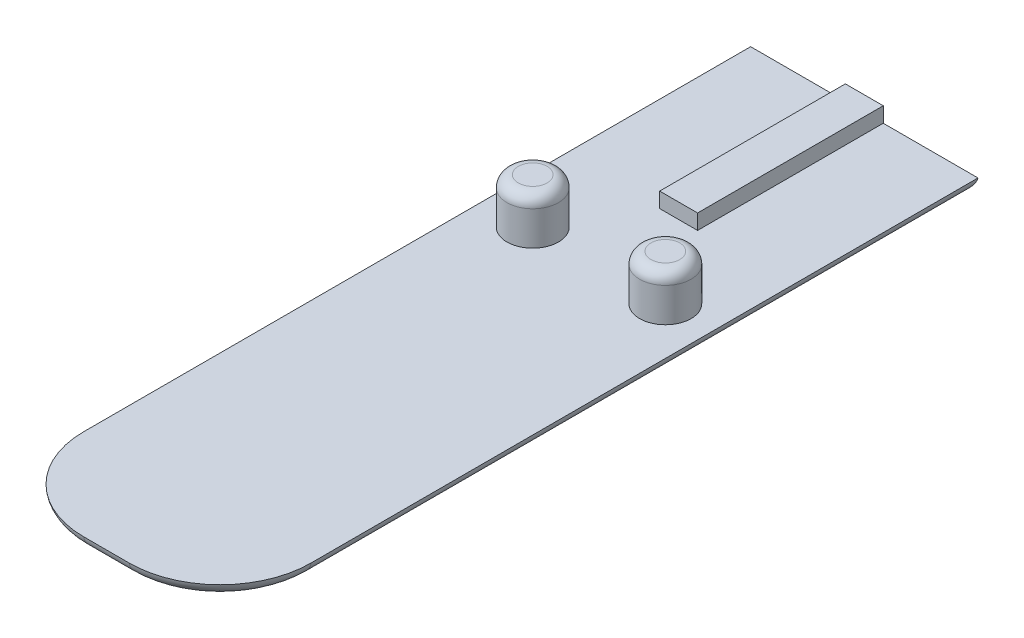
SolidWorks part; units mm, degrees
ref_plane "Front Plane" through (0, 0, 0) normal (0, 0, 1) x (1, 0, 0)
ref_plane "Top Plane" through (0, 0, 0) normal (0, 1, 0) x (1, 0, 0)
ref_plane "Right Plane" through (0, 0, 0) normal (1, 0, 0) x (0, 0, -1)
sketch "Sketch1" plane through (0, 0, 0) normal (0, 1, 0) x (1, 0, 0)
  line L0 (0, 50) -> (0, -50) construction
  line L1 (-15, -50) -> (15, -50)
  line L2 (-15, -50) -> (-15, 50)
  line L3 (-15, 50) -> (15, 50)
  line L4 (15, -50) -> (15, 50)
  line L5 (-15, -50) -> (15, 50) construction
  line L6 (-15, 50) -> (15, -50) construction
  point P0 (0, 0)
  dimension "D1" = 100
  dimension "D2" = 30
extrude "Boss-Extrude1" add sketch "Sketch1" along normal blind 1.7 contours L2 L1 L4 L3
fillet "Fillet2" radius 12 2 edges at (15, 0.85, 50) (-15, 0.85, 50)
fillet "Fillet3" radius 2 6 edges at (0, 0, -50) (-15, 0, -6) (-11.4853, 0, 46.4853) (0, 0, 50) (11.4853, 0, 46.4853) (15, 0, -6)
sketch "Sketch3" plane through (0, 1.7, 0) normal (0, 1, 0) x (1, 0, 0)
  line L2 (-15, 50) -> (15, 50) construction
  line L10 (-2.5, 50) -> (2.5, 50)
  line L12 (2.5, 25.5) -> (2.5, 49.5)
  line L18 (-2.5, 49.5) -> (-2.5, 25.5)
  line L19 (-2.5, 49.5) -> (-2.5, 50)
  line L20 (2.5, 49.5) -> (2.5, 50)
  line L21 (-3, 50) -> (-3, 2) construction
  line L22 (-2.5, 49.5) -> (2.5, 49.5) construction
  line L23 (-3, 2) -> (-7.3, 2) construction
  line L24 (-7.3, 2) -> (-7.3, -48) construction
  line L25 (-7.3, -48) -> (7.3, -48) construction
  line L26 (7.3, -48) -> (7.3, 2) construction
  line L27 (3, 2) -> (3, 50) construction
  line L28 (-3, 50) -> (3, 50) construction
  line L29 (7.3, 2) -> (3, 2) construction
  line L30 (-2.5, 25.5) -> (2.5, 25.5)
  line L31 (-2.5, 49.5) -> (-2.5, 1.5) construction
  line L32 (0, 25.5) -> (0, 50) construction
  line L33 (2.5, 1.5) -> (2.5, 49.5) construction
  line L34 (6.8, -47.5) -> (6.8, 1.5) construction
  line L35 (6.8, 1.5) -> (2.5, 1.5) construction
  line L36 (-2.5, 1.5) -> (-6.8, 1.5) construction
  line L37 (-6.8, 1.5) -> (-6.8, -47.5) construction
  line L38 (-6.8, -47.5) -> (6.8, -47.5) construction
  dimension "D8" = 0.5
extrude "Boss-Extrude2" add sketch "Sketch3" along normal blind 2
sketch "Sketch4" plane through (0, 1.7, 0) normal (0, 1, 0) x (1, 0, 0)
  line L0 (0, 50) -> (0, -50) construction
  line L1 (2.5, 50) -> (-2.5, 50) construction
  line L2 (-3, -50) -> (3, -50) construction
  line L3 (-8.75, 50) -> (-8.75, -51.1483) construction
  line L4 (-15, 50) -> (-2.5, 50) construction
  line L5 (8.75, 50) -> (8.75, -50.3997) construction
  line L6 (2.5, 50) -> (15, 50) construction
  line L7 (-15, 15) -> (15, 15) construction
  line L8 (-15, -38) -> (-15, 50) construction
  line L9 (15, -38) -> (15, 50) construction
  circle A0 centre (-8.75, 15) radius 3.4
  circle A1 centre (8.75, 15) radius 3.4
  dimension "D1" = 35
extrude "Boss-Extrude3" add sketch "Sketch4" along normal blind 6
fillet "Fillet4" radius 1.5 2 edges at (8.75, 7.7, -18.4) (-8.75, 7.7, -11.6)
